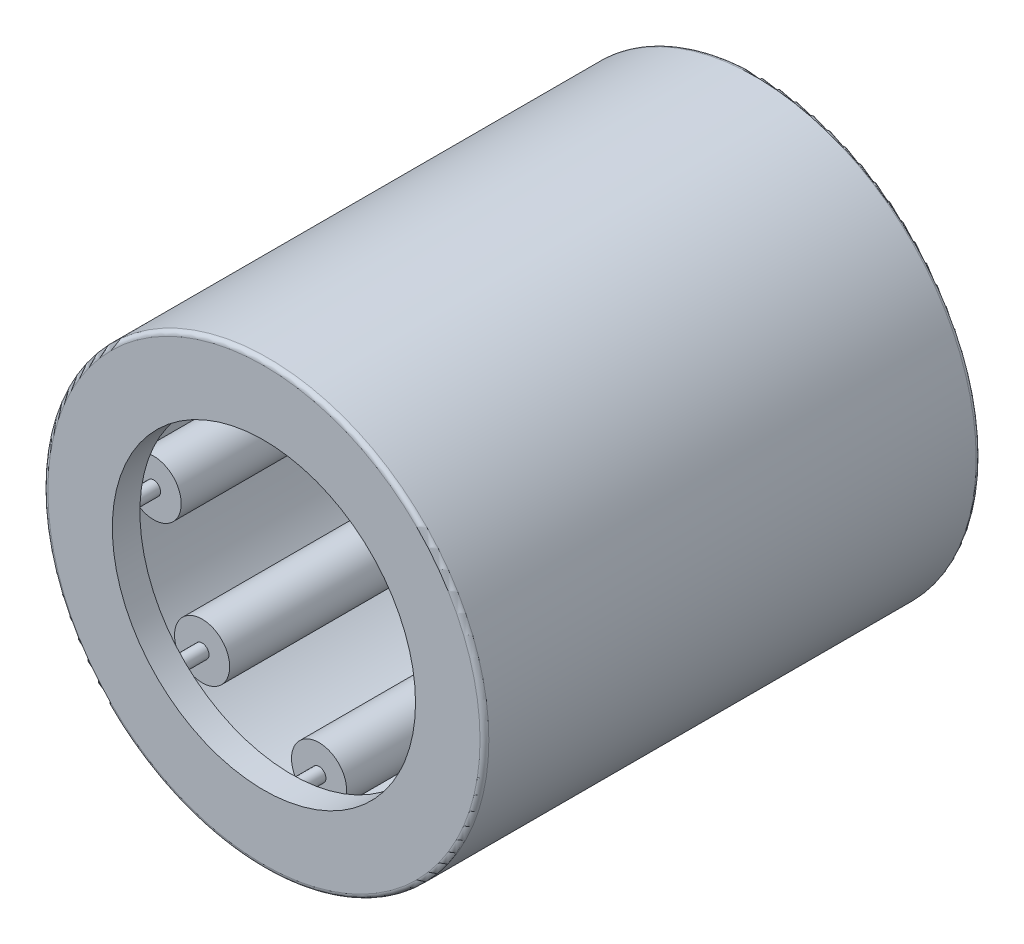
SolidWorks part; units mm, degrees
material "Plain Carbon Steel"
ref_plane "Front Plane" through (0, 0, 0) normal (0, 0, 1) x (1, 0, 0)
ref_plane "Top Plane" through (0, 0, 0) normal (0, 1, 0) x (1, 0, 0)
ref_plane "Right Plane" through (0, 0, 0) normal (1, 0, 0) x (0, 0, -1)
sketch "Sketch1" plane through (0, 0, 0) normal (1, 0, 0) x (0, 0, -1)
  line L0 (-7.1438, 0) -> (7.1437, 0) construction
  line L1 (0, 0) -> (0, 6.35) construction
  line L2 (-7.1438, 0) -> (-7.1438, 6.35) construction
  line L3 (-7.1438, 6.35) -> (7.1438, 6.35)
  line L4 (7.1438, 6.35) -> (7.1437, 0) construction
  line L5 (7.1437, 0) -> (6.35, 0) construction
  line L6 (6.35, 0) -> (6.35, 5.5563) construction
  line L7 (6.35, 5.5563) -> (-6.35, 5.5563)
  line L8 (-6.35, 5.5563) -> (-6.35, 0) construction
  line L9 (-6.35, 0) -> (-7.1438, 0) construction
  line L10 (-7.1438, 6.35) -> (-7.1438, 4.3656)
  line L11 (-7.1438, 4.3656) -> (-6.35, 4.3656)
  line L12 (-6.35, 4.3656) -> (-6.35, 5.5563)
  line L13 (6.35, 6.35) -> (6.35, 5.5563) construction
  line L14 (6.35, 5.5563) -> (6.35, 4.3656)
  line L15 (6.35, 4.3656) -> (7.1438, 4.3656)
  line L16 (7.1438, 4.3656) -> (7.1438, 6.35)
  line L17 (6.35, 5.5563) -> (6.35, 4.7625) construction
  line L18 (6.35, 4.7625) -> (6.35, 3.9687) construction
  point P5 (0, 3.9687)
  dimension "Width" = 14.2875
  dimension "OD" = 12.7
  dimension "Shaft Dia" = 7.9375
revolve "Revolve1" add sketch "Sketch1" angle 360 about L0
sketch "Sketch2" plane through (0, 0, 0) normal (1, 0, 0) x (0, 0, -1)
  line L0 (6.35, 5.5563) -> (-6.35, 5.5563) construction
  line L1 (-5.5563, 4.7625) -> (5.5563, 4.7625) construction
  line L2 (-5.5563, 4.7625) -> (-5.5563, 5.5563) construction
  line L3 (-5.5563, 5.5563) -> (5.5563, 5.5563)
  line L4 (5.5563, 4.7625) -> (5.5563, 5.5563) construction
  line L5 (6.35, 4.3656) -> (7.1438, 4.3656) construction
  line L6 (-6.35, 4.7625) -> (-5.5563, 4.7625) construction
  line L7 (5.5563, 4.7625) -> (6.35, 4.7625) construction
  line L8 (-7.1438, 4.3656) -> (-6.35, 4.3656) construction
  line L9 (-5.5563, 4.9609) -> (-5.5563, 4.5641) construction
  line L10 (-6.35, 4.7625) -> (-6.35, 4.3656) construction
  line L11 (-5.5563, 5.5563) -> (-5.5563, 4.9609)
  line L12 (5.5563, 5.5563) -> (5.5563, 4.9609)
  line L13 (5.5563, 4.9609) -> (-5.5563, 4.9609)
  line L14 (0, 5.5563) -> (0, 3.9687) construction
  line L15 (-6.35, 4.3656) -> (-6.35, 5.5563) construction
  line L16 (-5.5563, 4.5641) -> (-6.35, 4.5641) construction
  line L17 (0, 0) -> (7.1438, 0) construction
  line L31 (7.1438, -6.35) -> (7.1438, 6.35) construction
  point P16 (0, 4.7625)
revolve "Revolve2" add sketch "Sketch2" angle 360 about L1
sketch "Sketch3" plane through (0, 0, 0) normal (1, 0, 0) x (0, 0, -1)
  line L0 (6.35, 5.5563) -> (6.35, 4.3656) construction
  line L1 (-6.35, 4.7625) -> (6.35, 4.7625)
  line L2 (-6.35, 4.7625) -> (-6.35, 4.9609)
  line L3 (-6.35, 4.9609) -> (6.35, 4.9609)
  line L4 (6.35, 4.7625) -> (6.35, 4.9609)
  line L5 (0, 0) -> (7.1438, 0) construction
  line L6 (7.1438, -6.35) -> (7.1438, 6.35) construction
revolve "Revolve3" add sketch "Sketch3" angle 360 about L1
ref_axis "Axis1" through (0, 0, -7.1438) along (0, 0, 1)
pattern_circular "CirPattern1" count 8 every 45 about axis through (0, 0, -7.1438) along (0, 0, 1) of bodies 166 167
fillet "Fillet1" radius 0.127 2 edges at (6.35, 0, -7.1438) (6.35, 0, 7.1438)
sketch "Sketch4" plane through (0, 0, 0) normal (1, 0, 0) x (0, 0, -1)
  line L1 (7.0168, 3.9688) -> (5.5563, 3.9688)
  line L2 (7.0168, 3.9688) -> (7.0168, 4.3656)
  line L3 (7.0168, 4.3656) -> (5.5563, 4.3656)
  line L4 (5.5563, 3.9688) -> (5.5563, 4.3656)
  line L5 (-7.1438, 4.3656) -> (-6.35, 4.3656) construction
  line L6 (7.0168, -6.35) -> (7.0168, 6.35) construction
  line L7 (5.5563, 5.5563) -> (5.5563, 4.9609) construction
revolve "Revolve4" [suppressed] add sketch "Sketch4" angle 360 about L0
sketch "Sketch5" plane through (0, 0, 0) normal (1, 0, 0) x (0, 0, -1)
  line L0 (-7.0168, 6.35) -> (-7.0168, -6.35) construction
  line L1 (-5.5563, 3.9687) -> (-7.0168, 3.9687)
  line L2 (-5.5563, 3.9687) -> (-5.5563, 4.3656)
  line L3 (-5.5563, 4.3656) -> (-7.0168, 4.3656)
  line L4 (-7.0168, 3.9687) -> (-7.0168, 4.3656)
  line L6 (-5.5563, 5.5563) -> (-5.5563, 4.9609) construction
  line L7 (-7.1438, 4.3656) -> (-6.35, 4.3656) construction
revolve "Revolve5" [suppressed] add sketch "Sketch5" angle 360 about L0
sketch "Front View" plane through (0, 0, 0) normal (0, 0, 1) x (1, 0, 0)
  circle A0 centre (0, 0) radius 3.9688 construction
  circle A1 centre (0, 0) radius 6.35 construction
  dimension "OD" = 12.7
  dimension "ID" = 7.9375
sketch "Right View" plane through (0, 0, 0) normal (1, 0, 0) x (0, 0, -1)
  line L0 (-7.1437, 6.35) -> (7.1437, 6.35) construction
  dimension "Width" = 14.2875
ref_axis "Center Axis 1" through (0, 0, -7.0168) along (0, 0, 1)
ref_plane "Contact Plane 1" through (0, 0, 7.1438) normal (0, 0, 1) x (1, 0, 0)
ref_plane "Contact Plane 2" through (0, 0, -7.1438) normal (0, 0, -1) x (-1, 0, 0)
ref_axis "Axis2" through (0, 0, -7.0168) along (0, 0, 1)
equation "\"Rollers@CirPattern1\" = \"OD@Sketch1\"*16"
equation "\"D1@Fillet1\" = \"OD@Sketch1\"*.01"
equation "\"Angle@CirPattern1\"= 360 / \"Rollers@CirPattern1\""
equation "\"OD@Front View\"=\"OD@Sketch1\""
equation "\"ID@Front View\"=\"Shaft Dia@Sketch1\""
equation "\"Width@Right View\"=\"Width@Sketch1\""
